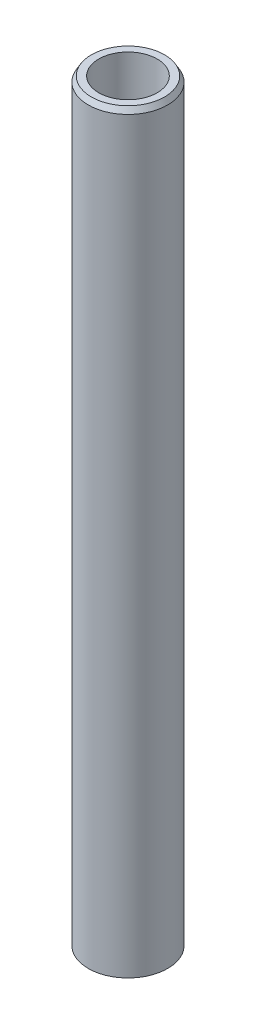
SolidWorks part; units mm, degrees
ref_plane "Front Plane" through (0, 0, 0) normal (0, 0, 1) x (1, 0, 0)
ref_plane "Top Plane" through (0, 0, 0) normal (0, 1, 0) x (1, 0, 0)
ref_plane "Right Plane" through (0, 0, 0) normal (1, 0, 0) x (0, 0, -1)
sketch "Sketch1" plane through (0, 0, 0) normal (0, 1, 0) x (1, 0, 0)
  circle A0 centre (0, 0) radius 30
  dimension "SHAFT_OD" = 60
extrude "Boss-Extrude1" add sketch "Sketch1" along normal blind 571.6757
sketch "Sketch2" plane through (0, 0, 0) normal (0, 1, 0) x (1, 0, 0)
  circle A0 centre (0, 0) radius 22.123
  dimension "BORE_D" = 44.2461
extrude "Cut-Extrude1" cut sketch "Sketch2" along normal through all
chamfer "Chamfer1" distance 4.0575 angle 30 2 edges at (0, 571.6757, 30) (0, 0, 30) first distance on face at (0, 571.6757, 30) first distance on face at (0, 0, 22.123)
